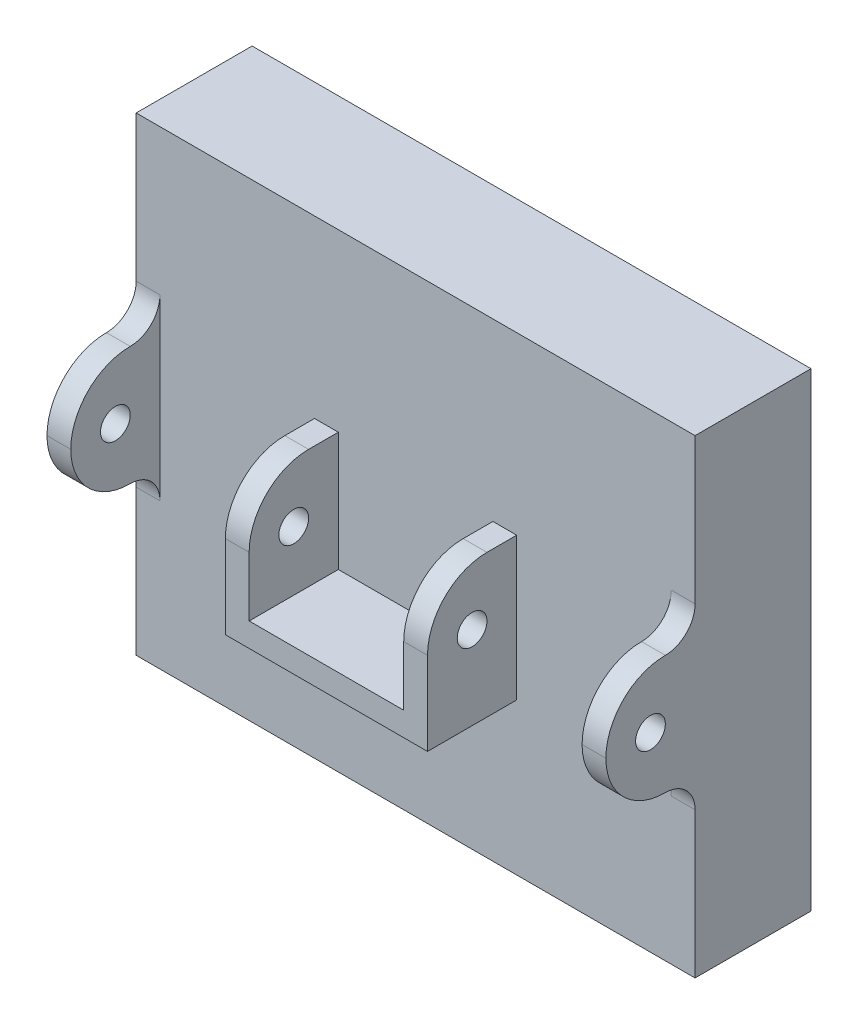
SolidWorks part; units mm, degrees
material "Buche"
ref_plane "Ebene vorne" through (0, 0, 0) normal (0, 0, 1) x (1, 0, 0)
ref_plane "Ebene oben" through (0, 0, 0) normal (0, 1, 0) x (1, 0, 0)
ref_plane "Ebene rechts" through (0, 0, 0) normal (1, 0, 0) x (0, 0, -1)
sketch "Skizze1" plane through (0, 0, 0) normal (0, 0, 1) x (1, 0, 0)
  line L1 (-94, -79) -> (94, -79)
  line L2 (-94, -79) -> (-94, 79)
  line L3 (-94, 79) -> (94, 79)
  line L4 (94, -79) -> (94, 79)
  line L5 (-94, -79) -> (94, 79) construction
  line L6 (-94, 79) -> (94, -79) construction
  point P0 (0, 0)
  dimension "D1" = 158
  dimension "D2" = 188
extrude "Aufsatz-Linear austragen1" add sketch "Skizze1" along normal blind 39
sketch "Skizze2" plane through (0, 0, 0) normal (0, 0, 1) x (1, 0, 0)
  line L1 (-90, 75) -> (90, 75)
  line L2 (-90, 75) -> (-90, -75)
  line L3 (-90, -75) -> (90, -75)
  line L4 (90, 75) -> (90, -75)
  line L5 (-90, 75) -> (90, -75) construction
  line L6 (-90, -75) -> (90, 75) construction
  point P0 (0, 0)
  dimension "D1" = 150
  dimension "D2" = 180
extrude "Schnitt-Linear austragen1" cut sketch "Skizze2" along normal blind 35 contours L4 L1 L2 L3 region at (0, 0, 0)
sketch "Skizze3" plane through (0, 0, 39) normal (0, 0, 1) x (1, 0, 0)
  line L1 (-94, 79) -> (-94, -79) construction
  line L2 (-94, 20) -> (-86, 20)
  line L3 (-86, 20) -> (-86, -20)
  line L4 (-86, -20) -> (-94, -20)
  line L6 (94, 79) -> (-94, 79) construction
  line L7 (-94, -79) -> (94, -79) construction
  line L8 (0, 79) -> (0, -79) construction
  line L14 (-94, 0) -> (94, 0) construction
  line L15 (-94, 20) -> (-94, -20)
  line L16 (-34, 20) -> (-26, 20)
  line L17 (-26, 20) -> (-26, -20)
  line L18 (-34, 20) -> (-34, -20)
  line L20 (-34, 0) -> (154, 0) construction
  line L21 (26, 20) -> (34, 20)
  line L22 (34, 20) -> (34, -20)
  line L23 (26, 20) -> (26, -20)
  line L25 (26, 0) -> (214, 0) construction
  line L26 (86, 20) -> (94, 20)
  line L27 (94, 20) -> (94, -20)
  line L28 (86, 20) -> (86, -20)
  line L29 (94, -20) -> (86, -20)
  line L30 (86, 0) -> (274, 0) construction
  line L32 (-26, -20) -> (26, -20)
  line L33 (-34, -20) -> (-34, -28)
  line L34 (-34, -28) -> (34, -28)
  line L35 (34, -20) -> (34, -28)
  line L36 (-26, -20) -> (-34, -20) [skipped]
  line L37 (34, -20) -> (26, -20) [skipped]
  point P35 (0, 0)
  point P36 (0, 0)
  dimension "D1" = 4
  dimension "D2" = 8
  dimension "D3" = 68
extrude "Aufsatz-Linear austragen2" add sketch "Skizze3" along normal blind 30
fillet "Verrundung1" radius 20 6 edges at (-90, -20, 69) (-90, 20, 69) (30, 20, 69) (-30, 20, 69) (90, -20, 69) (90, 20, 69)
sketch "Skizze4" plane through (-94, 0, 0) normal (-1, 0, 0) x (0, 0, 1)
  line L1 (49, 0) -> (59, 0) construction
  circle A3 centre (54, 0) radius 5
extrude "Schnitt-Linear austragen2" cut sketch "Skizze4" against normal blind 208
fillet "Verrundung2" radius 10 4 edges at (-90, 20, 39) (-90, -20, 39) (90, 20, 39) (90, -20, 39)
